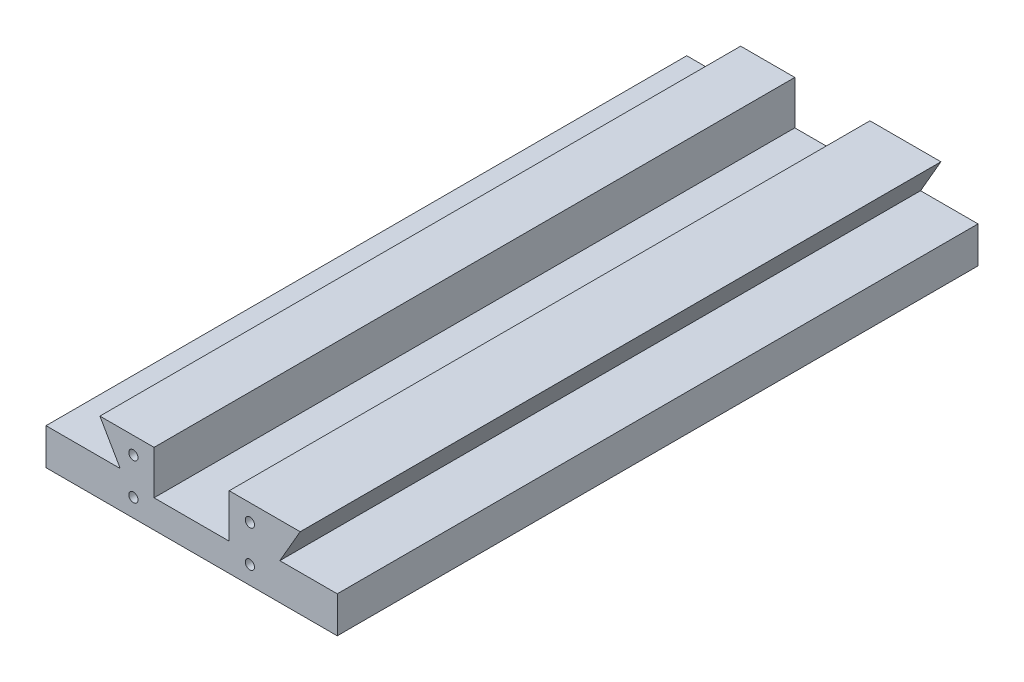
SolidWorks part; units mm, degrees
material "Ductile Iron"
ref_plane "Front Plane" through (0, 0, 0) normal (0, 0, 1) x (1, 0, 0)
ref_plane "Top Plane" through (0, 0, 0) normal (0, 1, 0) x (1, 0, 0)
ref_plane "Right Plane" through (0, 0, 0) normal (1, 0, 0) x (0, 0, -1)
sketch "Sketch6" plane through (0, 0, 0) normal (0, 0, 1) x (1, 0, 0)
  line B0 (-63.5, 0) -> (63.5, 0)
  line B1 (63.5, 0) -> (63.5, 15.875)
  line B2 (63.5, 15.875) -> (38.4596, 15.875)
  line B3 (38.4596, 15.875) -> (47.625, 31.75)
  line B4 (47.625, 31.75) -> (16.0563, 31.75)
  line B5 (-40.2927, 31.75) -> (-31.1272, 15.875)
  line B6 (-31.1272, 15.875) -> (-63.5, 15.875)
  line B7 (-63.5, 15.875) -> (-63.5, 0)
  line B8 (-38.4596, 15.875) -> (-47.625, 31.75)
  line B9 (-47.625, 31.75) -> (-40.2927, 31.75)
  line B10 (-16.0563, 31.75) -> (-16.0563, 12.7) construction
  line B11 (-16.0563, 12.7) -> (16.0563, 12.7) construction
  line B12 (16.0563, 12.7) -> (16.0563, 31.75) construction
  line B13 (-16.0563, 31.75) -> (-40.2927, 31.75)
  line B14 (-63.5, 15.875) -> (-63.5, 47.625)
  line B15 (-63.5, 47.625) -> (63.5, 47.625)
  line B16 (63.5, 47.625) -> (63.5, 15.875)
  line B17 (-16.0563, 31.75) -> (16.0563, 31.75) construction
  line B18 (0, 47.625) -> (0, 0) construction
  line B19 (-38.4596, 15.875) -> (38.4596, 15.875) construction
  line B20 (-28.702, 36.957) -> (28.702, 36.957) construction
  line B21 (-25.4, 7.874) -> (25.4, 7.874) construction
  line B22 (-25.4, 7.874) -> (-25.4, 23.8125) construction
  line B23 (25.4, 7.874) -> (25.4, 23.8125) construction
  line B24 (-52.832, 23.8125) -> (52.832, 23.8125) construction
  circle B25 centre (0, 22.225) radius 18.669 construction
  line B26 (40.2927, 31.75) -> (31.1272, 15.875)
  line B27 (31.1272, 15.875) -> (38.4596, 15.875)
  line B28 (-15.875, 31.75) -> (-15.875, 12.7)
  line B29 (-16.0563, 31.75) -> (-15.875, 31.75)
  line B30 (-15.875, 12.7) -> (15.875, 12.7)
  line B31 (15.875, 12.7) -> (15.875, 31.75)
  line B32 (15.875, 31.75) -> (16.0563, 31.75)
sketch_block_instance "dovetail pair-2"
sketch_block "dovetail pair" parameters "D8"=37.338, "D1"=60, "D2"=127, "D3"=6.35, "D4"=15.875, "D5"=31.75, "D6"=95.25, "D7"=19.05, "D9"=60, "D10"=31.75, "D11"=50.8, "D12"=23.876, "D13"=7.874, "D14"=10.668, "D15"=34.798, "D16"=21.082, "D17"=7.9375, "D18"=24.4437
sketch "dovetail-male-profile" plane through (0, 0, 0) normal (0, 0, 1) x (1, 0, 0)
  line L0 (47.3317, 31.242) -> (16.383, 31.242)
  line L1 (-16.383, 31.242) -> (-39.9994, 31.242)
  line L2 (16.383, 31.242) -> (16.383, 12.192)
  line L3 (16.383, 12.192) -> (-16.383, 12.192)
  line L4 (-16.383, 12.192) -> (-16.383, 31.242)
  line L5 (0, 47.625) -> (0, 0) construction
  line L7 (63.5, 15.875) -> (38.4596, 15.875) construction
  line L8 (63.5, 0) -> (63.5, 15.875) construction
  line L9 (-63.5, 0) -> (63.5, 0) construction
  line L10 (-63.5, 15.875) -> (-63.5, 0) construction
  line L11 (-31.1272, 15.875) -> (-63.5, 15.875) construction
  line L12 (38.4596, 15.875) -> (47.625, 31.75) construction
  line L13 (-31.1272, 15.875) -> (-39.9994, 31.242)
  line L15 (63.5, 15.875) -> (38.4596, 15.875)
  line L16 (63.5, 0) -> (63.5, 15.875)
  line L17 (-63.5, 0) -> (63.5, 0)
  line L18 (-63.5, 15.875) -> (-63.5, 0)
  line L19 (-31.1272, 15.875) -> (-63.5, 15.875)
  line L20 (-40.2927, 31.75) -> (-31.1272, 15.875) construction
  line L21 (38.4596, 15.875) -> (47.3317, 31.242)
  line L23 (47.625, 31.75) -> (16.0563, 31.75) construction
  line L25 (-16.0563, 12.7) -> (16.0563, 12.7) construction
  line L27 (15.875, 12.7) -> (15.875, 31.75) construction
  point P23 (0, 12.192)
  dimension "D2" = 0.508
  dimension "D1" = 0.508
  dimension "D3" = 0.508
extrude "x-guide-extrude" add sketch "dovetail-male-profile" along normal blind 279.4 contours L21 L0 L2 L3 L4 L1 L13 L19 L18 L17 L16 L15 region at (1.7017, 12.0113, 0)
hole_wizard "end plate holes" positions "Sketch2" profile "Sketch3" tap size "#10-32" standard "ANSI Inch"
sketch "Sketch2" plane through (0, 0, 0) normal (0, 0, -1) x (-1, 0, 0)
  point P27 (-25.4, 23.8125)
  point P29 (25.4, 23.8125)
  point P31 (25.4, 7.874)
  point P33 (-25.4, 7.874)
sketch "Sketch3" plane through (25.4, 23.8125, 0) normal (1, 0, 0) x (0, 1, 0)
  line L0 (0, 0) -> (0, 13.1513)
  line L1 (0, 13.1513) -> (2.0193, 11.938)
  line L2 (2.0193, 11.938) -> (2.0193, 0)
  line L3 (2.0193, 0) -> (0, 0)
  line L4 (0, 13.1513) -> (-2.0193, 11.938) construction
  line L5 (0, -6.35) -> (0, 107.95) construction
  dimension "Tap Drill Dia." = 4.0386
  dimension "Tap Drill Depth" = 11.938
  dimension "Drill Angle" = 118
cosmetic thread "Hole Thread1" parameters "D1"=9.652, "D2"=4.826
cosmetic thread "Hole Thread2" parameters "D1"=9.652, "D2"=4.826
cosmetic thread "Hole Thread9" parameters "D1"=9.652, "D2"=4.826
cosmetic thread "Hole Thread10" parameters "D1"=9.652, "D2"=4.826
hole_wizard "end plate holes 2" positions "Sketch4" profile "Sketch5" tap size "#10-32" standard "ANSI Inch"
sketch "Sketch4" plane through (0, 0, 279.4) normal (0, 0, 1) x (1, 0, 0)
  point P8 (25.4, 23.8125)
  point P10 (25.4, 7.874)
  point P12 (-25.4, 7.874)
  point P14 (-25.4, 23.8125)
cosmetic thread "Hole Thread5" parameters "D1"=9.652, "D2"=4.826
cosmetic thread "Hole Thread6" parameters "D1"=9.652, "D2"=4.826
cosmetic thread "Hole Thread11" parameters "D1"=9.652, "D2"=4.826
cosmetic thread "Hole Thread12" parameters "D1"=9.652, "D2"=4.826
sketch "Sketch5" plane through (25.4, 23.8125, 279.4) normal (1, 0, 0) x (0, -1, 0)
  line L0 (0, 0) -> (0, 13.1513)
  line L1 (0, 13.1513) -> (2.0193, 11.938)
  line L2 (2.0193, 11.938) -> (2.0193, 0)
  line L5 (2.0193, 0) -> (0, 0)
  line L10 (0, 13.1513) -> (-2.0193, 11.938) construction
  line L11 (0, -6.35) -> (0, 107.95) construction
  dimension "Tap Drill Dia." = 4.0386
  dimension "Tap Drill Depth" = 11.938
  dimension "Drill Angle" = 118
equation "\"dovetail-angle\" = 60"
equation "\"dovetail-stock-width\" = 5"
equation "\"dovetail-stock-height\" = 1.25"
equation "\"dovetail-throat-width\" = \"dovetail-stock-width\" - (2 * \"dovetail-depth\")"
equation "\"dovetail-depth\" = 0.5 * \"dovetail-stock-height\""
equation "\"delta-x\" = 6"
equation "\"delta-y\" = 3"
equation "\"gib-thickness\" = 0.25"
equation "\"x-slide-length\" = \"dovetail-stock-width\" + \"delta-x\""
equation "\"y-slide-length\" = \"dovetail-stock-width\" + \"delta-y\""
equation "\"D1@x-guide-extrude\"=\"x-slide-length\""
equation "\"dog-point-diam\" = .149"
equation "\"dog-point-length\" = .067"
equation "\"dovetail-double-height\" = 2 * \"dovetail-depth\" + 0.5"
equation "\"acme-major-diam\" = .5"
equation "\"acme-pitch-diam\" = 0.45"
equation "\"acme-minor-diam\" = 0.4"
equation "\"acme-nut-od\" = 1.47"
equation "\"acme-nut-length\" = 1"
equation "\"acme-nut-trim-height\" = .75"
equation "\"screw-bearing-od\" = 0.5"
equation "\"screw-bearing-length\" = .375"
equation "\"end-plate-thickness\" = \"screw-bearing-length\""
equation "\"screw-bearing-id\" = .3125"
equation "\"screw-add-length\" = 2 * \"end-plate-thickness\" + 1 + 0.5"
equation "\"acme-nut-mount-hole-space-horz\" = 0.95"
equation "\"acme-nut-mount-hole-space-vert\" = 0.5 * \"acme-nut-length\""
equation "\"x-screw-length\" = \"x-slide-length\" + \"screw-add-length\""
equation "\"y-screw-length\" = \"y-slide-length\" + \"screw-add-length\""
equation "\"D2@dovetail pair\"=\"dovetail-stock-width\""
equation "\"D1@dovetail pair\"=\"dovetail-angle\""
equation "\"D3@dovetail pair\"=\"gib-thickness\""
equation "\"D4@dovetail pair\"=\"dovetail-depth\""
equation "\"D5@dovetail pair\"=\"dovetail-stock-height\""
equation "\"D6@dovetail pair\"=\"dovetail-throat-width\""
equation "\"D10@dovetail pair\"=\"dovetail-stock-height\""
equation "\"D7@dovetail pair\"=\"acme-nut-trim-height\""
equation "\"D8@dovetail pair\"=\"acme-nut-od\""
equation "\"D9@dovetail pair\"=\"dovetail-angle\""
equation "\"D17@dovetail pair\"=\"dovetail-depth\"/2"
equation "\"acme-nut-trim-width\" = 1.25"
equation "\"vise-hole-center-dist\" = 6.75"
equation "\"wiper_plate_clearance\" = .03"
equation "\"dial-width\" = 0.5"
equation "\"quarter-twenty-free-fit\" = .2667"
equation "\"acme_nut_clearance\" = .02"
equation "\"dovetail_male_clearance\" = .02"
equation "\"D1@dovetail-male-profile\"=\"dovetail_male_clearance\""
equation "\"D2@dovetail-male-profile\"=\"dovetail_male_clearance\""
equation "\"D3@dovetail-male-profile\"=\"dovetail_male_clearance\""
